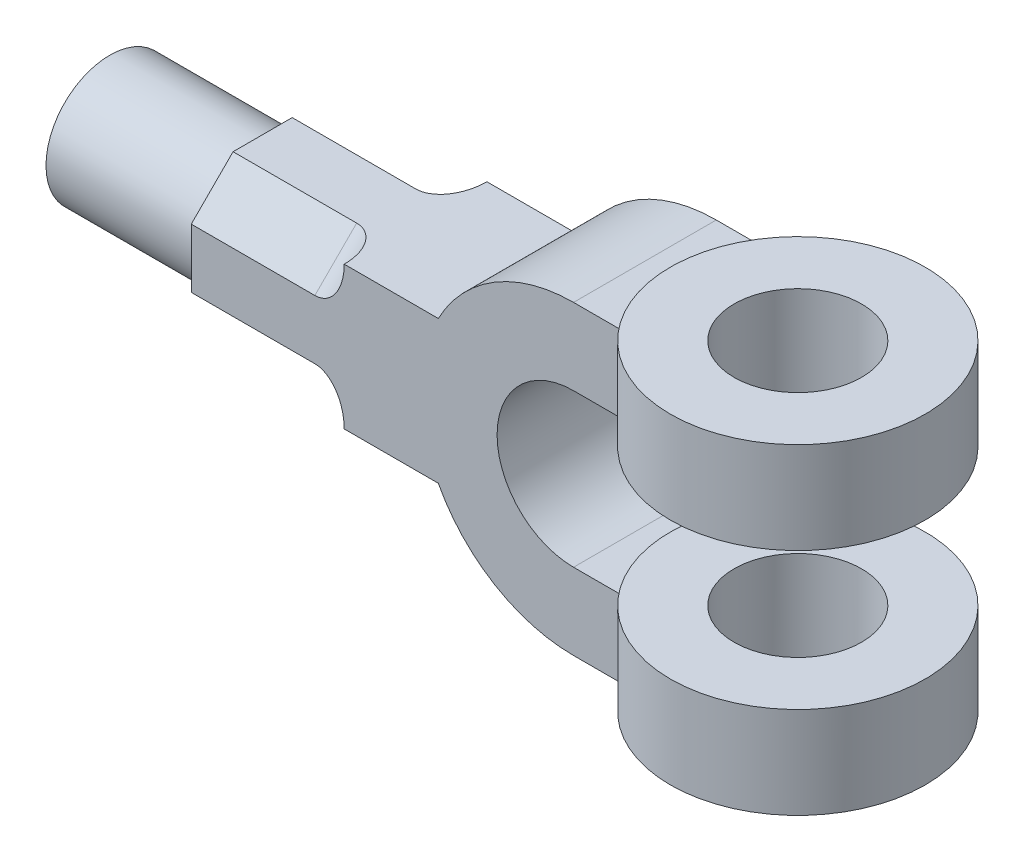
SolidWorks part; units mm, degrees
ref_plane "Front Plane" through (0, 0, 0) normal (0, 0, 1) x (1, 0, 0)
ref_plane "Top Plane" through (0, 0, 0) normal (0, 1, 0) x (1, 0, 0)
ref_plane "Right Plane" through (0, 0, 0) normal (1, 0, 0) x (0, 0, -1)
sketch "Sketch1" plane through (0, 0, 0) normal (0, 0, 1) x (1, 0, 0)
  line L1 (5, 31.5) -> (55, 31.5)
  line L2 (0, -30) -> (5, -30)
  line L3 (-45, 14) -> (-45, -14)
  line L4 (-26.533, 14) -> (-45, 14)
  line L5 (0, -30) -> (55, -30) construction
  line L6 (0, 30) -> (5, 30)
  line L7 (5, 31.5) -> (5, 30)
  line L8 (-26.533, -14) -> (-45, -14)
  line L9 (55, -13.5) -> (55, -31.5)
  line L10 (55, 13.5) -> (55, 31.5)
  line L11 (5, -31.5) -> (55, -31.5)
  line L12 (5, 30) -> (5, 15)
  line L13 (5, -15) -> (5, -30)
  line L14 (0, 15) -> (5, 15)
  line L15 (5, 13.5) -> (5, 15)
  line L16 (5, -31.5) -> (5, -30)
  line L17 (1.5, -31.5) -> (55, -31.5) construction
  line L18 (5, 13.5) -> (55, 13.5)
  line L19 (0, -15) -> (5, -15)
  line L20 (5, -13.5) -> (5, -15)
  line L21 (0, -30) -> (0, -40.2004) construction
  line L22 (1.5, -31.5) -> (1.5, -38.7004) construction
  line L23 (1.5, -38.7004) -> (15, -38.7004) construction
  line L24 (0, -40.2004) -> (15, -40.2004) construction
  line L25 (5, -13.5) -> (55, -13.5)
  line L26 (-26.533, 14) -> (-26.533, -14)
  arc A0 (0, 15) -> (0, -15) centre (0, 0) ccw
  arc A1 (-26.533, -14) -> (0, -30) centre (0, 0) ccw
  arc A2 (0, 30) -> (-26.533, 14) centre (0, 0) ccw
  dimension "D1" = 30
  dimension "D2" = 60
  dimension "D6" = 5
  dimension "D3" = 5
  dimension "D4" = 5
  dimension "D5" = 5
  dimension "D8" = 50
  dimension "D7" = 1.5
extrude "Boss-Extrude1" add sketch "Sketch1" along normal mid plane 50 contours L15 L18 L10 L1 L7 L12 | L25 L20 L13 L16 L11 L9 region at (30, 22.5, 0) region at (30, -22.5, 0)
extrude "Boss-Extrude2" add sketch "Sketch1<4>" along normal mid plane 28 contours L6 A2 L26 A1 L2 L13 L19 A0 L14 L12 region at (4.3222, 22.5, 0)
sketch "Sketch1<4>" plane through (0, 0, 0) normal (0, 0, 1) x (1, 0, 0) same geometry as "Sketch1"
extrude "Boss-Extrude3" add sketch "Sketch1<5>" along normal mid plane 28 contours L26 L4 L3 L8 region at (-35.7665, 0, 0)
sketch "Sketch1<5>" plane through (0, 0, 0) normal (0, 0, 1) x (1, 0, 0) same geometry as "Sketch1"
sketch "Sketch2" plane through (0, 31.5, 0) normal (0, 1, 0) x (1, 0, 0)
  line L0 (30, -25) -> (30, 25) construction
  line L1 (5, -25) -> (55, -25) construction
  line L2 (5, 25) -> (55, 25) construction
  line L3 (5, 0) -> (55, 0) construction
  line L4 (5, -25) -> (5, 25) construction
  line L5 (55, -25) -> (55, 25) construction
  circle A0 centre (30, 0) radius 25
  circle A1 centre (30, 0) radius 12.5
  dimension "D1" = 25
extrude "Cut-Extrude1" cut sketch "Sketch2" against normal blind 98 contours A1
sketch "Sketch3" plane through (0, 31.5, 0) normal (0, 1, 0) x (1, 0, 0)
  line L0 (5, -25) -> (5, 25)
  line L1 (5, 25) -> (55, 25)
  line L2 (55, 25) -> (55, -25)
  line L3 (55, -25) -> (5, -25)
  circle A0 centre (30, 0) radius 25
  line M6 (55, 25) -> (5, 25)
  line M7 (5, 25) -> (5, -25)
  line M8 (5, -25) -> (55, -25)
  line M9 (55, -25) -> (55, 25)
extrude "Cut-Extrude2" cut sketch "Sketch3" against normal blind 98 contours A0 L0 M8 | A0 L1 M7 | A0 L3 M9 | A0 L2 M6 region at (10.5842, 31.5, 19.4158) region at (10.5842, 31.5, -19.4158) region at (49.4158, 31.5, 19.4158) region at (49.4158, 31.5, -19.4158)
sketch "Sketch5" plane through (5, 0, 0) normal (1, 0, 0) x (0, 0, -1)
ref_plane "Plane1" through (0, 30, 0) normal (0, 1, 0) x (1, 0, 0)
sketch "Sketch6" plane through (0, 30, 0) normal (0, 1, 0) x (1, 0, 0)
  line L0 (5, 14) -> (9.2877, 14)
  line L1 (5, -14) -> (9.2877, -14)
  line L2 (5, 14) -> (5, -14)
  arc A0 (9.2877, -14) -> (9.2877, 14) centre (30, 0) cw
extrude "Boss-Extrude4" add sketch "Sketch6" against normal blind 15 contours L2 A0 L0 | L1 A0 L2 | A0 L0 L2 L1 region at (6.2649, 30, 10.5629) region at (6.2649, 30, -10.5629)
ref_plane "Plane2" through (0, -30, 0) normal (0, -1, 0) x (-1, 0, 0)
sketch "Sketch7" plane through (0, -30, 0) normal (0, -1, 0) x (-1, 0, 0)
  line L0 (-5, 14) -> (-9.2877, 14)
  line L1 (-5, 14) -> (-5, -14)
  line L2 (-5, -14) -> (-9.2877, -14)
  arc A0 (-9.2877, -14) -> (-9.2877, 14) centre (-30, 0) ccw
extrude "Boss-Extrude5" add sketch "Sketch7" against normal blind 15 contours A0 L1 L0 | A0 L2 L1 | A0 L0 L1 L2 region at (6.2649, -30, -10.5629) region at (6.2649, -30, 10.5629)
sketch "Sketch8" plane through (-45, 0, 0) normal (-1, 0, 0) x (0, 0, 1)
  line L0 (14, 14) -> (-14, 14) construction
  line L1 (5.799, 14) -> (-5.799, 14)
  line L2 (-5.799, 14) -> (-14, 5.799)
  line L3 (-14, 5.799) -> (-14, -5.799)
  line L4 (-14, -5.799) -> (-5.799, -14)
  line L5 (-5.799, -14) -> (5.799, -14)
  line L6 (5.799, -14) -> (14, -5.799)
  line L7 (14, -5.799) -> (14, 5.799)
  line L8 (14, 5.799) -> (5.799, 14)
  line L9 (14, 14) -> (14, -14) construction
  line L10 (14, -14) -> (-14, -14) construction
  line L11 (-14, 14) -> (-14, -14) construction
  circle A0 centre (0, 0) radius 14 construction
extrude "Boss-Extrude6" add sketch "Sketch8" along normal blind 30
fillet "Fillet1" radius 5.75 1 edges at (-45, 9.8995, -9.8995) type face fillet first side face at (-45, 11.2663, -11.2663) second side face at (-60, 9.8995, -9.8995)
fillet "Fillet2" radius 5.75 1 edges at (-45, 9.8995, 9.8995) type face fillet first side face at (-45, 11.2663, 11.2663) second side face at (-60, 9.8995, 9.8995)
fillet "Fillet3" radius 5.75 1 edges at (-45, -9.8995, -9.8995) type face fillet first side face at (-45, -11.2663, -11.2663) second side face at (-60, -9.8995, -9.8995)
fillet "Fillet4" radius 5.75 1 edges at (-45, -9.8995, 9.8995) type face fillet first side face at (-45, -11.2663, 11.2663) second side face at (-60, -9.8995, 9.8995)
sketch "Sketch9" plane through (-75, 0, 0) normal (-1, 0, 0) x (0, 0, 1)
  circle A0 centre (0, 0) radius 12.5
  dimension "D1" = 25
extrude "Boss-Extrude7" add sketch "Sketch9" along normal blind 30
